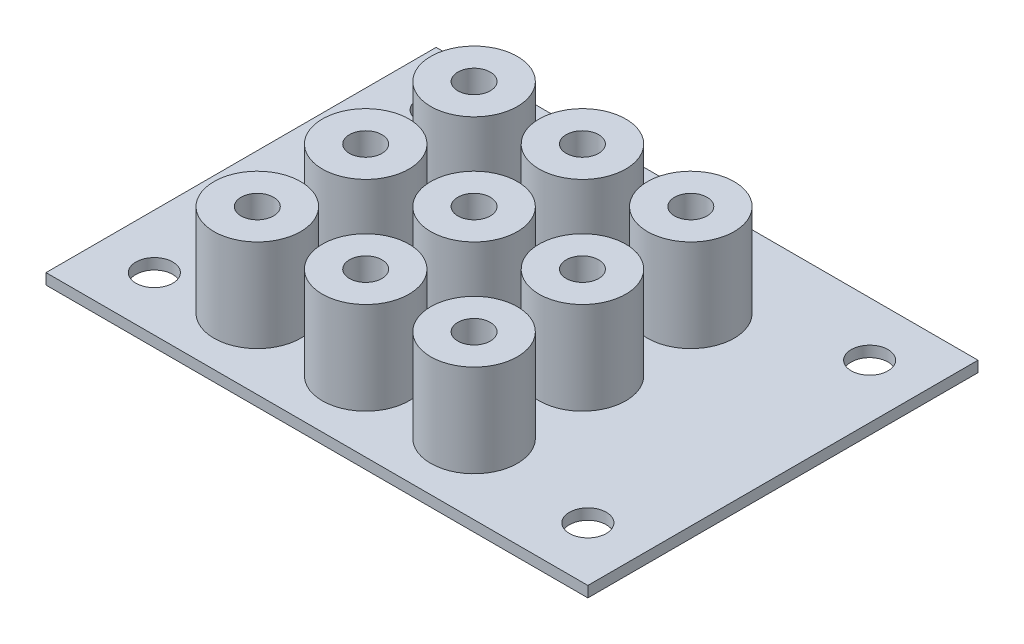
SolidWorks part; units mm, degrees
ref_plane "Front Plane" through (0, 0, 0) normal (0, 0, 1) x (1, 0, 0)
ref_plane "Top Plane" through (0, 0, 0) normal (0, 1, 0) x (1, 0, 0)
ref_plane "Right Plane" through (0, 0, 0) normal (1, 0, 0) x (0, 0, -1)
sketch "Sketch1" plane through (0, 0, 0) normal (0, 1, 0) x (1, 0, 0)
  line L0 (45, 31) -> (5, 31) construction
  line L1 (0, 0) -> (50, 0)
  line L2 (0, 0) -> (0, 36)
  line L3 (0, 36) -> (50, 36)
  line L4 (50, 0) -> (50, 36)
  line L6 (45, 31) -> (45, 5) construction
  circle A19 centre (13, 6.5) radius 1.25
  circle A28 centre (5, 5) radius 1.7
  circle A29 centre (5, 31) radius 1.7
  circle A30 centre (45, 31) radius 1.7
  circle A31 centre (45, 5) radius 1.7
  circle A32 centre (23, 6.5) radius 1.25
  circle A33 centre (33, 6.5) radius 1.25
  circle A34 centre (23, 16.5) radius 1.25
  circle A35 centre (33, 16.5) radius 1.25
  circle A36 centre (23, 26.5) radius 1.25
  circle A37 centre (33, 26.5) radius 1.25
  circle A38 centre (13, 16.5) radius 1.25
  circle A39 centre (13, 26.5) radius 1.25
  point P7 (45, 18)
  point P9 (25, 31)
  point P10 (25, 36)
  point P20 (50, 18)
  dimension "D5" = 40
  dimension "D6" = 26
  dimension "D3" = 2.5
  dimension "D8" = 3.4
  dimension "D1" = 50
  dimension "D2" = 36
  dimension "D4" = 8
  dimension "D7" = 1.5
  dimension "D9" = 3
extrude "Boss-Extrude1" add sketch "Sketch1" along normal blind 1 contours L1 L4 L3 L2 A39 A36 A34 region at (25.0514, 0, -18.0385)
sketch "Sketch2" plane through (0, 1, 0) normal (0, 1, 0) x (1, 0, 0)
  circle A0 centre (13, 26.5) radius 1.5
  circle A1 centre (13, 26.5) radius 1.25 construction
  circle A2 centre (13, 26.5) radius 4
  circle A3 centre (23, 26.5) radius 4
  circle A4 centre (23, 26.5) radius 1.5
  circle A5 centre (33, 26.5) radius 4
  circle A6 centre (33, 26.5) radius 1.5
  circle A7 centre (23, 16.5) radius 4
  circle A8 centre (23, 16.5) radius 1.5
  circle A9 centre (33, 16.5) radius 4
  circle A10 centre (33, 16.5) radius 1.5
  circle A11 centre (23, 6.5) radius 4
  circle A12 centre (23, 6.5) radius 1.5
  circle A13 centre (33, 6.5) radius 4
  circle A14 centre (33, 6.5) radius 1.5
  circle A15 centre (13, 16.5) radius 4
  circle A16 centre (13, 16.5) radius 1.5
  circle A17 centre (13, 6.5) radius 4
  circle A18 centre (13, 6.5) radius 1.5
  dimension "D1" = 3
  dimension "D2" = 8
extrude "Boss-Extrude2" add sketch "Sketch2" along normal blind 8.525
equation "\"o\"= 10mm"
equation "\"P\"= 10"
